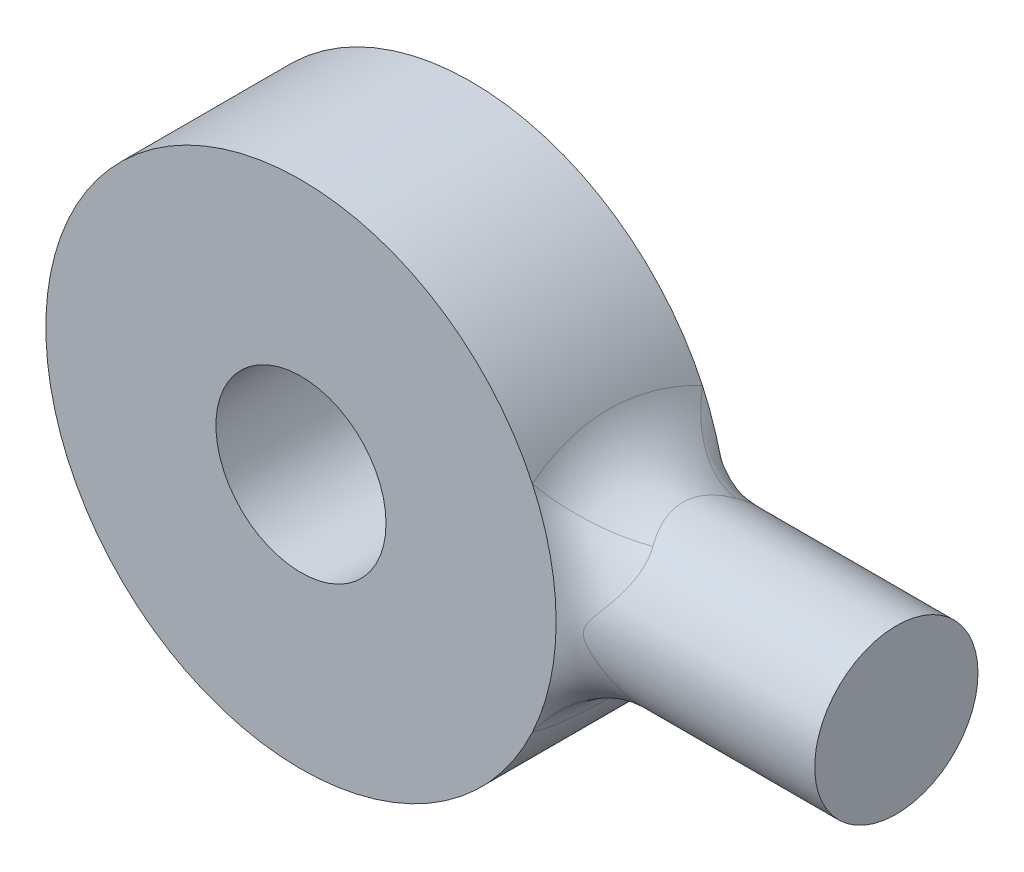
SolidWorks part; units mm, degrees
ref_plane "Front Plane" through (0, 0, 0) normal (0, 0, 1) x (1, 0, 0)
ref_plane "Top Plane" through (0, 0, 0) normal (0, 1, 0) x (1, 0, 0)
ref_plane "Right Plane" through (0, 0, 0) normal (1, 0, 0) x (0, 0, -1)
sketch "Sketch1" plane through (0, 0, 0) normal (0, 0, 1) x (1, 0, 0)
  circle A0 centre (0, 0) radius 9.525
  circle A1 centre (0, 0) radius 3.175
  dimension "D1" = 19.05
  dimension "D2" = 6.35
extrude "Boss-Extrude1" add sketch "Sketch1" along normal mid plane 6.35
sketch "Sketch4" plane through (0, 0, 0) normal (0, 0, 1) x (1, 0, 0)
  line L0 (6.35, 0) -> (19.05, 0)
  dimension "D1" = 6.35
  dimension "D2" = 12.7
sweep "Sweep1" add path "Sketch4" circular profile diameter 6.096 parameters "D3"=6.096
fillet "Fillet1" radius 3.175 1 edges at (9.5101, 0.5318, 3.0013)
ref_point "Point1"
